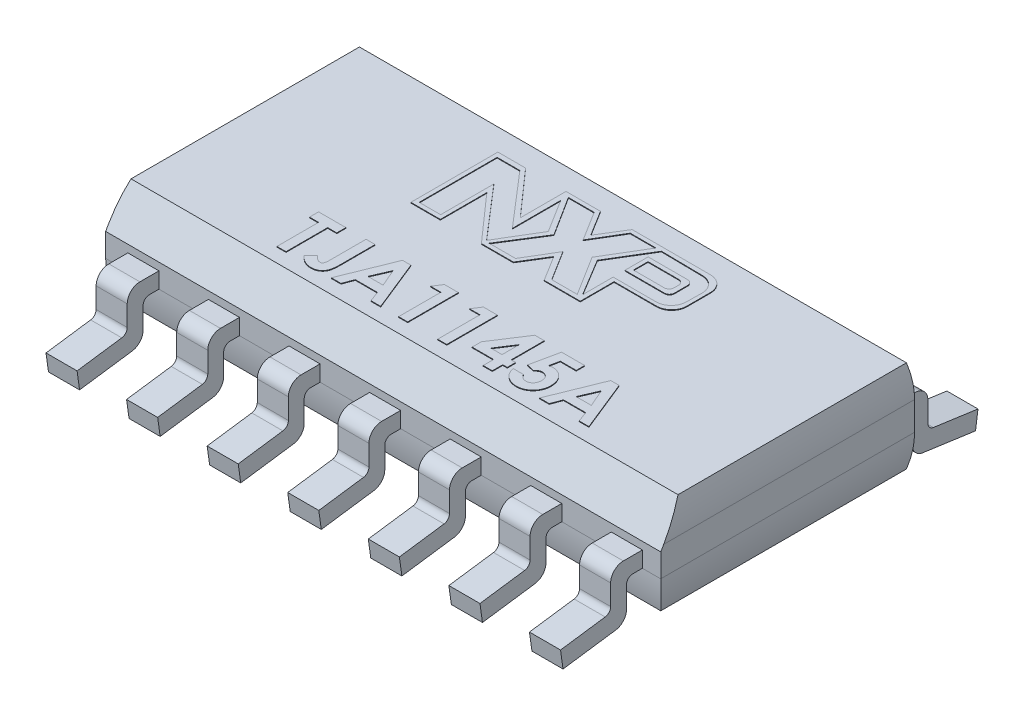
SolidWorks part; units mm, degrees
ref_plane "Front Plane" through (0, 0, 0) normal (0, 0, 1) x (1, 0, 0)
ref_plane "Top Plane" through (0, 0, 0) normal (0, 1, 0) x (1, 0, 0)
ref_plane "Right Plane" through (0, 0, 0) normal (1, 0, 0) x (0, 0, -1)
sketch "Sketch1" plane through (0, 0, 0) normal (0, 1, 0) x (1, 0, 0)
  line L1 (-4.375, 2) -> (4.375, 2)
  line L2 (-4.375, 2) -> (-4.375, -2)
  line L3 (-4.375, -2) -> (4.375, -2)
  line L4 (4.375, 2) -> (4.375, -2)
  line L5 (-4.375, 2) -> (4.375, -2) construction
  line L6 (-4.375, -2) -> (4.375, 2) construction
  point P0 (0, 0)
  dimension "D1" = 8.75
  dimension "D2" = 4
extrude "Boss-Extrude1" add sketch "Sketch1" along normal blind 1.45
sketch "Sketch2" plane through (-4.375, 0, 0) normal (-1, 0, 0) x (0, 0, 1)
  line L0 (2, 0.8687) -> (1.6644, 1.45)
  line L1 (2, 1.45) -> (2, 0) construction
  line L2 (-2, 1.45) -> (2, 1.45) construction
  line L3 (0, 0) -> (0, 0.828) construction
  line L4 (-2, 0.725) -> (-1.3983, 0.725) construction
  line L6 (-2, 1.45) -> (-2, 0) construction
  line L7 (-1.8644, 1.6722) -> (-2.1559, 1.6722)
  line L8 (-2.1559, 1.6722) -> (-2.1559, 0.954)
  line L9 (-2.1559, 0.954) -> (-2, 0.9484)
  line L10 (-2, 0.5016) -> (-2.1559, 0.5016)
  line L11 (-2.1559, 0.5016) -> (-2.1559, -0.2223)
  line L12 (-2.1559, -0.2223) -> (-1.8644, -0.2222)
  line L13 (1.6644, 1.45) -> (1.6644, 1.7317)
  line L14 (1.6644, 1.7317) -> (2.4871, 1.7317)
  line L15 (2.4871, 1.7317) -> (2.4871, 0.8687)
  line L16 (2.4871, 0.8687) -> (2, 0.8687)
  line L17 (2, 0.5015) -> (2.4871, 0.5015)
  line L18 (2.4871, 0.5015) -> (2.4871, -0.2223)
  line L19 (2.4871, -0.2223) -> (1.8644, -0.2223)
  arc A0 (2, 0.5015) -> (1.8644, -0.2223) centre (0, 0.5016) cw
  arc A1 (-2, 0.5016) -> (-1.8644, -0.2222) centre (0, 0.5016) ccw
  arc A2 (-2, 0.9484) -> (-1.8644, 1.6722) centre (0, 0.9484) cw
  dimension "D1" = 2
  dimension "D2" = 60
extrude "Cut-Extrude1" cut sketch "Sketch2" against normal blind 61.45
sketch "Sketch5" plane through (0, 0, -2) normal (0, 0, -1) x (-1, 0, 0)
  line L1 (0, 1.45) -> (0, 1.0867) construction
  line L2 (-5.1778, 0.725) -> (-4.5761, 0.725) construction
  line L3 (-4.2394, 1.6723) -> (-4.5309, 1.6723)
  line L4 (-4.5309, 1.6723) -> (-4.5309, 0.954)
  line L5 (-4.5309, 0.954) -> (-4.375, 0.9484)
  line L6 (-4.375, 0.5016) -> (-4.5309, 0.5016)
  line L7 (-4.5309, 0.5016) -> (-4.5309, -0.2223)
  line L8 (-4.5309, -0.2223) -> (-4.2394, -0.2223)
  line L16 (4.375, 1.45) -> (-4.375, 1.45) construction
  line L17 (-4.5309, 1.6723) -> (-4.2394, 1.6723)
  line L18 (-4.5309, 0.9484) -> (-4.5309, 1.6723)
  line L19 (-4.375, 0.9484) -> (-4.5309, 0.9484)
  line L20 (-4.5309, 0.496) -> (-4.375, 0.5016)
  line L21 (-4.5309, -0.2223) -> (-4.5309, 0.496)
  line L22 (-4.2394, -0.2223) -> (-4.5309, -0.2223)
  line L23 (4.5309, -0.2223) -> (4.2394, -0.2223)
  line L24 (4.5309, 0.5016) -> (4.5309, -0.2223)
  line L25 (4.375, 0.5016) -> (4.5309, 0.5016)
  line L26 (4.5309, 0.954) -> (4.375, 0.9484)
  line L27 (4.5309, 1.6723) -> (4.5309, 0.954)
  line L28 (4.2394, 1.6723) -> (4.5309, 1.6723)
  arc A1 (-4.375, 0.5016) -> (-4.2394, -0.2223) centre (-2.375, 0.5015) ccw
  arc A2 (-4.375, 0.9484) -> (-4.2394, 1.6723) centre (-2.375, 0.9485) cw
  arc A3 (-4.375, 0.5016) -> (-4.2394, -0.2223) centre (-2.375, 0.5015) ccw
  arc A4 (-4.375, 0.9484) -> (-4.2394, 1.6723) centre (-2.375, 0.9485) cw
  arc A5 (4.375, 0.5016) -> (4.2394, -0.2223) centre (2.375, 0.5015) cw
  arc A6 (4.375, 0.9484) -> (4.2394, 1.6723) centre (2.375, 0.9485) ccw
extrude "Cut-Extrude2" cut sketch "Sketch5" against normal blind 61.45 contours L5 A2 L3 L4 | A1 L20 L7 L22 | A6 L26 L27 L28 | L25 A5 L23 L24 region at (4.4265, 1.352, -2) region at (4.4265, 0.0979, -2) region at (-4.4266, 0.0992, -2) region at (-4.4265, 1.352, -2)
sketch "Sketch6" plane through (-4.375, 0, 0) normal (-1, 0, 0) x (0, 0, 1)
  line L5 (1.9361, 0) -> (-1.9361, 0) construction
  line L7 (0, 0) -> (0, -0.7239) construction
  line L8 (2.2535, 0.75) -> (2.3, 0.75)
  line L9 (2.5, 0.55) -> (2.5, 0.2276)
  line L10 (2.5, 0.1406) -> (3.25, 0.1406) construction
  line L11 (3.25, 0.1406) -> (3.25, -0.1094) construction
  line L12 (3.25, -0.1094) -> (2.25, -0.1094) construction
  line L13 (2.25, 0.0645) -> (2.25, 0.4)
  line L14 (2.25, 0.5) -> (2.2535, 0.5)
  line L15 (-3.25, -0.1094) -> (-2.25, -0.1094) construction
  line L17 (2.4222, -0.1335) -> (3.2508, -0.25)
  line L18 (2.5861, 0.1286) -> (3.2901, 0.0296)
  line L19 (3.2508, -0.25) -> (3.2901, 0.0296)
  line L20 (-3.25, 0.1406) -> (-3.25, -0.1094) construction
  line L21 (-2.5, 0.1406) -> (-3.25, 0.1406) construction
  line L22 (-3.2508, -0.25) -> (-3.2901, 0.0296)
  line L23 (-2.5861, 0.1286) -> (-3.2901, 0.0296)
  line L24 (-2.4222, -0.1335) -> (-3.2508, -0.25)
  line L25 (-2.25, 0.5) -> (-2.2535, 0.5)
  line L26 (-2.25, 0.0645) -> (-2.25, 0.4)
  line L27 (-2.5, 0.55) -> (-2.5, 0.2276)
  line L28 (-2.2535, 0.75) -> (-2.3, 0.75)
  line L29 (-2.15, 0.5) -> (2.15, 0.5)
  line L30 (-2.2535, 0.75) -> (2.2535, 0.75)
  arc A0 (2.4222, -0.1335) -> (2.25, 0.0645) centre (2.45, 0.0645) cw
  arc A1 (2.5, 0.55) -> (2.3, 0.75) centre (2.3, 0.55) ccw
  arc A2 (2.5861, 0.1286) -> (2.5, 0.2276) centre (2.6, 0.2276) cw
  arc A3 (2.25, 0.4) -> (2.15, 0.5) centre (2.15, 0.4) ccw
  arc A4 (-2.25, 0.4) -> (-2.15, 0.5) centre (-2.15, 0.4) cw
  arc A5 (-2.5861, 0.1286) -> (-2.5, 0.2276) centre (-2.6, 0.2276) ccw
  arc A6 (-2.5, 0.55) -> (-2.3, 0.75) centre (-2.3, 0.55) cw
  arc A7 (-2.4222, -0.1335) -> (-2.25, 0.0645) centre (-2.45, 0.0645) ccw
  line M15 (-2, 0.9484) -> (-2, 0.5016)
  line M17 (2, 0.5016) -> (2, 0.8687)
  dimension "D9" = 0.2
  dimension "D10" = 0.1
  dimension "D4" = 0.25
  dimension "D5" = 0.25
  dimension "D6" = 1
  dimension "D7" = 8
  dimension "D8" = 0.25
extrude "Boss-Extrude2" add sketch "Sketch6" against normal up to surface (8.75 mm away) contours L30 M15 M17 | L24 A7 L26 A4 L29 A3 L13 A0 L17 L19 L18 A2 L9 A1 L8 L30 L28 A6 L27 A5 L23 L22 region at (-4.375, 0.6834, 2.2768) up to face at (4.375, 0.8431, 0.3908)
sketch "Sketch7" plane through (0, 1.45, 0) normal (0, 1, 0) x (1, 0, 0)
  line L0 (4.375, -2) -> (-4.375, -2) construction
  line L1 (-4.375, -2) -> (-4.025, -2)
  line L2 (-4.375, -2) -> (-4.375, -3.534)
  line L3 (-4.375, -3.534) -> (-4.025, -3.534)
  line L4 (-4.025, -2) -> (-4.025, -3.534)
  line L5 (-3.535, -2) -> (-2.755, -2)
  line L6 (-3.535, -2) -> (-3.535, -3.6106)
  line L7 (-3.535, -3.6106) -> (-2.755, -3.6106)
  line L8 (-2.755, -2) -> (-2.755, -3.6106)
  line L9 (0, 0) -> (-3.4858, 0) construction
  line L10 (-2.265, -2) -> (-1.485, -2)
  line L11 (-2.265, -2) -> (-2.265, -3.6106)
  line L12 (-2.265, -3.6106) -> (-1.485, -3.6106)
  line L13 (-1.485, -2) -> (-1.485, -3.6106)
  line L14 (1.055, -2) -> (0.275, -2)
  line L15 (1.055, -2) -> (1.055, -3.783)
  line L16 (1.055, -3.783) -> (0.275, -3.783)
  line L17 (0.275, -2) -> (0.275, -3.783)
  line L18 (-0.215, -2) -> (-0.995, -2)
  line L19 (-0.215, -2) -> (-0.215, -3.6776)
  line L20 (-0.215, -3.6776) -> (-0.995, -3.6776)
  line L21 (-0.995, -2) -> (-0.995, -3.6776)
  line L22 (-0.995, 2) -> (-0.995, 3.6776)
  line L23 (-0.215, 3.6776) -> (-0.995, 3.6776)
  line L24 (-0.215, 2) -> (-0.215, 3.6776)
  line L25 (-0.215, 2) -> (-0.995, 2)
  line L26 (0.275, 2) -> (0.275, 3.783)
  line L27 (1.055, 3.783) -> (0.275, 3.783)
  line L28 (1.055, 2) -> (1.055, 3.783)
  line L29 (1.055, 2) -> (0.275, 2)
  line L30 (-1.485, 2) -> (-1.485, 3.6106)
  line L31 (-2.265, 3.6106) -> (-1.485, 3.6106)
  line L32 (-2.265, 2) -> (-2.265, 3.6106)
  line L33 (-2.265, 2) -> (-1.485, 2)
  line L34 (-2.755, 2) -> (-2.755, 3.6106)
  line L35 (-3.535, 3.6106) -> (-2.755, 3.6106)
  line L36 (-3.535, 2) -> (-3.535, 3.6106)
  line L37 (-3.535, 2) -> (-2.755, 2)
  line L38 (-4.025, 2) -> (-4.025, 3.534)
  line L39 (-4.375, 3.534) -> (-4.025, 3.534)
  line L40 (-4.375, 2) -> (-4.375, 3.534)
  line L41 (-4.375, 2) -> (-4.025, 2)
  line L42 (4.375, -2) -> (-4.375, -2) construction
  line L43 (1.545, -2) -> (2.325, -2)
  line L44 (1.545, -2) -> (1.545, -3.783)
  line L45 (1.545, -3.783) -> (2.325, -3.783)
  line L46 (2.325, -2) -> (2.325, -3.783)
  line L47 (4.085, 2) -> (4.085, 3.8801)
  line L48 (2.815, -2) -> (3.595, -2)
  line L49 (2.815, -2) -> (2.815, -4.1331)
  line L50 (2.815, -4.1331) -> (3.595, -4.1331)
  line L51 (3.595, -2) -> (3.595, -4.1331)
  line L52 (4.375, -2) -> (4.085, -2)
  line L53 (4.375, -2) -> (4.375, -3.8801)
  line L54 (4.375, -3.8801) -> (4.085, -3.8801)
  line L55 (4.085, -2) -> (4.085, -3.8801)
  line L56 (4.375, 3.8801) -> (4.085, 3.8801)
  line L57 (4.375, 2) -> (4.375, 3.8801)
  line L58 (4.375, 2) -> (4.085, 2)
  line L59 (3.595, 2) -> (3.595, 4.1331)
  line L60 (2.815, 4.1331) -> (3.595, 4.1331)
  line L61 (2.815, 2) -> (2.815, 4.1331)
  line L62 (2.815, 2) -> (3.595, 2)
  line L63 (2.325, 2) -> (2.325, 3.783)
  line L64 (1.545, 3.783) -> (2.325, 3.783)
  line L65 (1.545, 2) -> (1.545, 3.783)
  line L66 (1.545, 2) -> (2.325, 2)
  point P62 (4.085, -2.9401)
  dimension "D1" = 0.49
  dimension "D2" = 0.49
  dimension "D3" = 0.49
  dimension "D4" = 0.49
  dimension "D5" = 0.78
  dimension "D6" = 0.78
  dimension "D7" = 0.78
  dimension "D8" = 0.35
  dimension "D9" = 0.49
  dimension "D10" = 0.49
  dimension "D11" = 0.78
  dimension "D12" = 0.78
  dimension "D13" = 0.78
  dimension "D14" = 0.49
extrude "Cut-Extrude3" cut sketch "Sketch7" against normal blind 61.45 body kept at (4.375, 0.8687, 2)
sketch "Sketch8" plane through (0, 1.45, 0) normal (0, 1, 0) x (1, 0, 0)
  line L0 (70.6653, 255.7964) -> (518.6653, 255.7964) construction
  line L1 (-1.775, 0.2105) -> (-1.775, 1.5827)
  line L2 (-1.775, 1.5827) -> (-1.3388, 1.5827)
  line L3 (-1.3388, 1.5827) -> (-0.7012, 0.8616)
  line L4 (-0.7012, 0.8616) -> (-0.7012, 1.5827)
  line L5 (-0.7012, 1.5827) -> (-0.1577, 1.5827)
  line L6 (-0.1577, 1.5827) -> (0.092, 1.1801)
  line L7 (0.092, 1.1801) -> (0.3406, 1.5827)
  line L8 (0.3406, 1.5827) -> (1.577, 1.5827)
  line L9 (1.817, 1.3427) -> (1.817, 0.9698)
  line L10 (1.577, 0.7298) -> (0.91, 0.7298)
  line L11 (0.91, 0.7298) -> (0.91, 0.1964)
  line L12 (0.91, 0.1964) -> (0.3406, 0.1964)
  line L13 (0.3406, 0.1964) -> (0.092, 0.5973)
  line L14 (0.092, 0.5973) -> (-0.1512, 0.2035)
  line L15 (-0.1512, 0.2035) -> (-0.6559, 0.2035)
  line L16 (-0.6559, 0.2035) -> (-1.3094, 0.9426)
  line L17 (-1.3094, 0.9426) -> (-1.3094, 0.2105)
  line L18 (-1.3094, 0.2105) -> (-1.775, 0.2105)
  line L19 (-1.7094, 0.2766) -> (-1.7094, 1.5045)
  line L20 (-1.7094, 1.5045) -> (-1.3506, 1.5045)
  line L21 (-1.3506, 1.5045) -> (-0.6198, 0.6555)
  line L22 (-0.6198, 0.6555) -> (-0.6198, 1.4187)
  line L23 (-0.6198, 1.4187) -> (-0.2937, 0.8962)
  line L24 (-0.2937, 0.8962) -> (-0.6592, 0.288)
  line L25 (-0.6592, 0.288) -> (-1.3716, 1.1155)
  line L26 (-1.3716, 1.1155) -> (-1.3716, 0.2766)
  line L27 (-1.3716, 0.2766) -> (-1.7094, 0.2766)
  line L28 (-0.5996, 1.5187) -> (-0.1938, 1.5187)
  line L29 (-0.1938, 1.5187) -> (0.0963, 1.0543)
  line L30 (0.0963, 1.0543) -> (0.3747, 1.5187)
  line L31 (0.3747, 1.5187) -> (0.7798, 1.5187)
  line L32 (0.7798, 1.5187) -> (0.4027, 0.8897)
  line L33 (0.4027, 0.8897) -> (0.7926, 0.2655)
  line L34 (0.7926, 0.2655) -> (0.3902, 0.2655)
  line L35 (0.3902, 0.2655) -> (0.0963, 0.736)
  line L36 (0.0963, 0.736) -> (-0.1833, 0.2695)
  line L37 (-0.1833, 0.2695) -> (-0.5996, 0.2695)
  line L38 (-0.5996, 0.2695) -> (-0.205, 0.8962)
  line L39 (-0.205, 0.8962) -> (-0.5996, 1.5187)
  line L40 (0.8664, 1.5187) -> (1.5222, 1.5095)
  line L41 (1.7588, 1.2662) -> (1.7554, 1.0214)
  line L42 (1.5154, 0.7847) -> (0.8395, 0.7847)
  line L43 (0.8395, 0.7847) -> (0.8395, 0.3024)
  line L44 (0.8395, 0.3024) -> (0.4854, 0.8897)
  line L45 (0.4854, 0.8897) -> (0.8664, 1.5187)
  line L46 (0.8395, 1.3362) -> (1.4613, 1.3362)
  line L47 (1.5413, 1.2562) -> (1.5413, 1.0498)
  line L48 (1.4613, 0.9698) -> (0.8395, 0.9698)
  line L49 (0.8395, 1.3362) -> (0.8395, 0.9698)
  line L50 (0.9038, 1.2698) -> (1.3866, 1.2698)
  line L51 (0.9038, 1.2698) -> (0.9038, 1.0405)
  line L52 (0.9038, 1.0405) -> (1.3866, 1.0405)
  line L53 (1.4666, 1.1898) -> (1.4666, 1.1205)
  arc A0 (1.817, 0.9698) -> (1.577, 0.7298) centre (1.577, 0.9698) cw
  arc A1 (1.577, 1.5827) -> (1.817, 1.3427) centre (1.577, 1.3427) cw
  arc A2 (1.7554, 1.0214) -> (1.5154, 0.7847) centre (1.5154, 1.0247) cw
  arc A3 (1.5222, 1.5095) -> (1.7588, 1.2662) centre (1.5188, 1.2695) cw
  arc A4 (1.3866, 1.0405) -> (1.4666, 1.1205) centre (1.3866, 1.1205) ccw
  arc A5 (1.3866, 1.2698) -> (1.4666, 1.1898) centre (1.3866, 1.1898) cw
  arc A6 (1.5413, 1.0498) -> (1.4613, 0.9698) centre (1.4613, 1.0498) cw
  arc A7 (1.4613, 1.3362) -> (1.5413, 1.2562) centre (1.4613, 1.2562) cw
extrude "Boss-Extrude3" add sketch "Sketch8" along normal blind 0.01 contours A1 L8 L7 L6 L5 L4 L3 L2 L1 L18 L17 L16 L15 L14 L13 L12 L11 L10 A0 L9 L38 L39 L28 L29 L30 L31 L32 L33 L34 L35 L36 L37 L26 L27 L19 L20 L21 L22 L23 L24 L25 L40 A3 L41 A2 L42 L43 L44 | A7 L46 L49 L48 A6 L47 L50 A5 L53 A4 L52 L51 region at (-1.7365, 1.45, -0.8966) region at (1.1504, 1.45, -1.3282)
sketch "Sketch9" plane through (0, 1.45, 0) normal (0, 1, 0) x (1, 0, 0)
  line L0 (-2.3826, -1.4465) -> (3.2848, -1.4465) construction
  text T0 "<b>TJA1145A</b>" font "Century Gothic" height 0.8
extrude "Boss-Extrude4" add sketch "Sketch9" along normal blind 0.01
